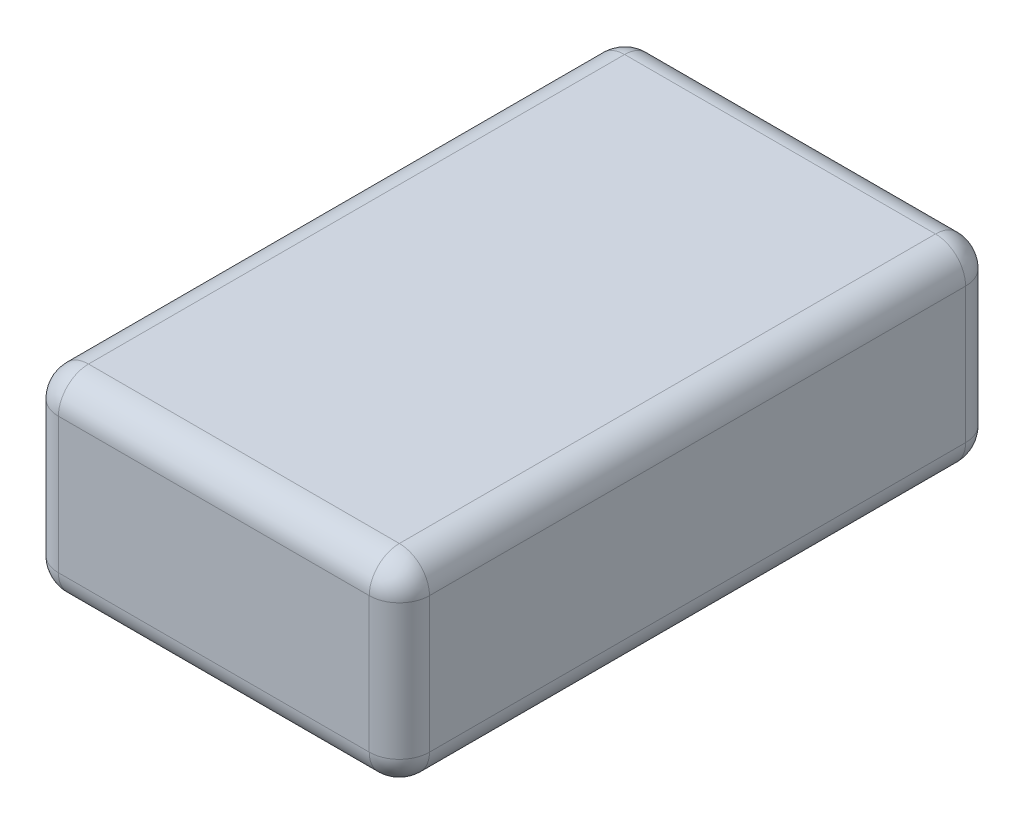
SolidWorks part; units mm, degrees
ref_plane "Front Plane" through (0, 0, 0) normal (0, 0, 1) x (1, 0, 0)
ref_plane "Top Plane" through (0, 0, 0) normal (0, 1, 0) x (1, 0, 0)
ref_plane "Right Plane" through (0, 0, 0) normal (1, 0, 0) x (0, 0, -1)
sketch "Sketch1" plane through (0, 0, 0) normal (0, 0, 1) x (1, 0, 0)
  line L1 (0, 0) -> (123.2, 0)
  line L2 (0, 0) -> (0, 65)
  line L3 (0, 65) -> (123.2, 65)
  line L4 (123.2, 0) -> (123.2, 65)
  dimension "D1" = 123.2
  dimension "D2" = 65
extrude "Boss-Extrude1" add sketch "Sketch1" along normal blind 198 contours L4 L3 L2 L1
fillet "Fillet1" radius 10 4 edges at (61.6, 65, 198) (61.6, 65, 0) (0, 65, 99) (123.2, 65, 99)
fillet "Fillet2" radius 10 4 edges at (61.6, 0, 198) (61.6, 0, 0) (0, 0, 99) (123.2, 0, 99)
fillet "Fillet3" radius 10 12 edges at (120.2711, 62.0711, 2.9289) (120.2711, 62.0711, 195.0711) (2.9289, 62.0711, 195.0711) (2.9289, 62.0711, 2.9289) (0, 32.5, 0) (123.2, 32.5, 0) (0, 32.5, 198) (123.2, 32.5, 198) (2.9289, 2.9289, 2.9289) (2.9289, 2.9289, 195.0711) (120.2711, 2.9289, 195.0711) (120.2711, 2.9289, 2.9289)
